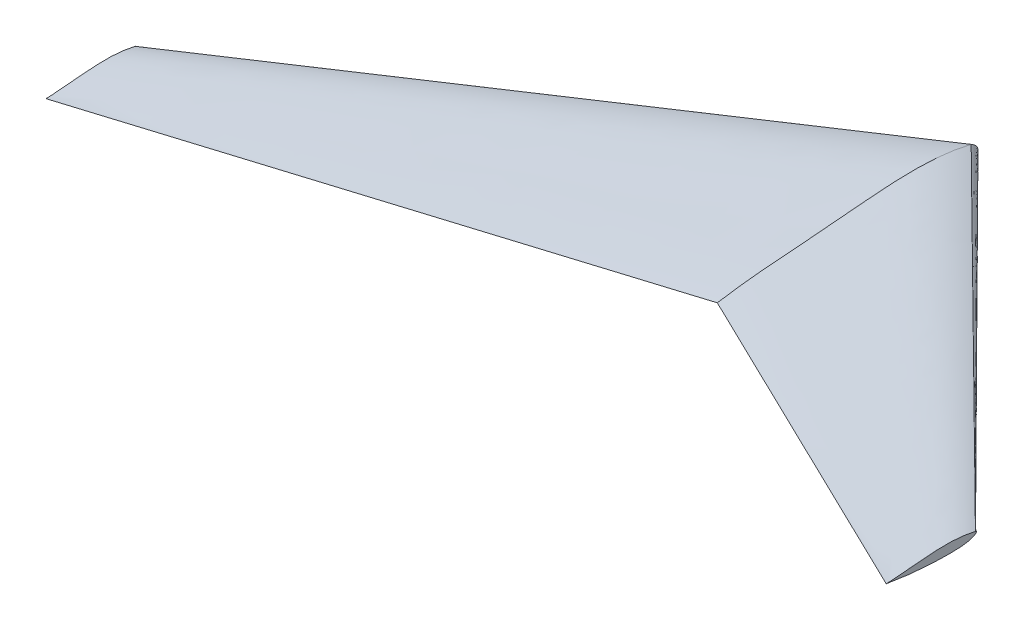
SolidWorks part; units mm, degrees
ref_plane "Front Plane" through (0, 0, 0) normal (0, 0, 1) x (1, 0, 0)
ref_plane "Top Plane" through (0, 0, 0) normal (0, 1, 0) x (1, 0, 0)
ref_plane "Right Plane" through (0, 0, 0) normal (1, 0, 0) x (0, 0, -1)
sketch "Sketch2" plane through (0, 0, 0) normal (0, 1, 0) x (1, 0, 0)
  line L0 (0, -6122.228) -> (0, 2040.7427)
  line L1 (0, 0) -> (-18096.1342, 0) construction
  line L2 (0, 0) -> (-21640.8, -16307.5125) construction
  line L3 (-21640.8, -18450.2946) -> (-21640.8, -15593.2518)
  line L4 (-21640.8, -15593.2518) -> (0, 2040.7427)
  line L5 (-21640.8, -18450.2946) -> (0, -6122.228)
  line L6 (-9083.802, -5361.1886) -> (-9083.802, -6845.1358) construction
  line L7 (-9083.802, -6845.1358) -> (-9083.802, -11296.9774) construction
  line L8 (-9083.802, -6845.1358) -> (0, -6845.1358) construction
  line L9 (0, 408.1485) -> (-18440.4, -13713.752)
  line L10 (0, -35661.6) -> (-7316.724, -42249.6079) construction
  line L11 (0, -35661.6) -> (-8167.6786, -35661.6) construction
  line L12 (0, -34539.0879) -> (0, -39029.1363)
  line L13 (-7316.724, -43428.2455) -> (-7316.724, -41856.7287)
  line L14 (-7316.724, -41856.7287) -> (0, -34539.0879)
  line L15 (0, -39029.1363) -> (-7316.724, -43428.2455)
  line L16 (-2544.3607, -37083.7674) -> (-2544.3607, -37952.5526) construction
  line L17 (-2544.3607, -37952.5526) -> (-2544.3607, -40558.9084) construction
  line L18 (-2544.3607, -37952.5526) -> (0, -37952.5526) construction
  line L19 (-18440.4, -13713.752) -> (-18440.4, -15898.787)
  line L20 (-18440.4, -15898.787) -> (0, -4489.6339)
  line L21 (0, 408.1485) -> (0, -4489.6339) construction
  line L22 (0, -4489.6339) -> (0, 408.1485) construction
  line L23 (0, 408.1485) -> (0, -2040.7427) construction
  line L24 (0, 408.1485) -> (0, -4489.6339) construction
  line L25 (0, -2040.7427) -> (-18440.4, -14806.2695) construction
  line L26 (0, 408.1485) -> (-21640.8, -16164.6603) construction
  line L27 (-6975.7046, -4933.9377) -> (-6975.7046, -6869.7347) construction
  line L28 (-6975.7046, -6869.7347) -> (-6975.7046, -8805.5317) construction
  line L29 (-6975.7046, -6869.7347) -> (0, -6869.7347) construction
  dimension "Wing Sweep" = 37
  dimension "Half Span" = 21640.8
  dimension "Wing Root" = 8162.9707
  dimension "D4" = 2040.7427
  dimension "Wing Tip" = 2857.0428
  dimension "D6" = 714.2607
  dimension "Wing YBar" = 9083.802
  dimension "Tail Sweep" = 42
  dimension "Tail Root" = 4490.0484
  dimension "D10" = 1122.5121
  dimension "Tail Tip" = 1571.5168
  dimension "D12" = 392.8792
  dimension "D13" = 7316.724
  dimension "Tail Ybar" = 2544.3607
  dimension "First Spar" = 1632.5941
  dimension "Second Spar" = 6530.3766
  dimension "Fuel Tip" = 2185.035
  dimension "Tip Spar" = 571.4086
  dimension "Fuel Ybar" = 6975.7046
  dimension "Fuel Tank Length" = 18440.4
  dimension "Tail Arm" = 35661.6
sketch "Sketch4" plane through (0, 0, 0) normal (0, 1, 0) x (1, 0, 0)
  line L0 (0, 17538.8642) -> (0, -40677.9358) construction
  line L1 (-2194.56, 17538.8642) -> (2194.56, 17538.8642) construction
  line L2 (-2194.56, 10955.1842) -> (-2194.56, -31899.6958)
  line L3 (-2194.56, -40677.9358) -> (2194.56, -40677.9358) construction
  line L4 (2194.56, 10955.1842) -> (2194.56, -31899.6958)
  line L5 (0, -6122.228) -> (0, 2040.7427) construction
  line L6 (-9083.802, -6845.1358) -> (0, -6845.1358) construction
  line L7 (-2544.3607, -37952.5526) -> (0, -37952.5526) construction
  line L8 (0, 0) -> (-21640.8, -16307.5125) construction
  line L9 (-21640.8, -15593.2518) -> (0, 2040.7427) construction
  line L10 (-8474.964, 1555.5245) -> (-5807.964, 1555.5245)
  line L11 (-8474.964, 1555.5245) -> (-8474.964, -5453.2245)
  line L12 (-8474.964, -5453.2245) -> (-5807.964, -5453.2245)
  line L13 (-5807.964, 1555.5245) -> (-5807.964, -5453.2245)
  line L14 (2194.56, 10955.1842) -> (-2194.56, 10955.1842)
  arc A0 (-2194.56, -31899.6958) -> (2194.56, -31899.6958) centre (0, -31899.6958) ccw construction
  spline S0 degree 2 poles (-2194.56, 10955.1842) (-2319.3121, 14550.827) (0, 17538.8642) knots 0 0 0 1 1 1 construction
  spline S1 degree 2 poles (2194.56, 10955.1842) (2319.3121, 14550.827) (0, 17538.8642) knots 0 0 0 1 1 1 construction
  spline S2 degree 3 poles (-2194.56, -31899.6958) (-2185.0252, -17343.0176) (-1882.3736, -55849.4008) (-475.0937, -22625.7195) (0, -39029.1363) knots 0 0 0 0 0.566127 1 1 1 1 construction
  spline S3 degree 3 poles (2194.56, -31899.6958) (2185.0252, -17343.0176) (1882.3736, -55849.4008) (475.0937, -22625.7195) (0, -39029.1363) knots 0 0 0 0 0.566127 1 1 1 1 construction
  spline S4 degree 2 poles (-2194.56, -31899.6958) (-4104.2514, -24790.3016) (0, -27753.3552) knots 0 0 0 1 1 1
  spline S5 degree 2 poles (2194.56, -31899.6958) (4104.2514, -24790.3016) (0, -27753.3552) knots 0 0 0 1 1 1
  point P6 (0, 10955.1842)
  point P7 (0, -31899.6958)
  point P8 (0, -6845.1358)
  point P15 (0, -34094.2558)
  point P28 (-7141.464, 1555.5245)
  point P29 (-7141.464, -3778.4755)
  point P35 (-7141.464, -5381.4791)
  point P44 (-7141.464, -1247.9751)
  dimension "Fuse Length" = 58216.8
  dimension "Fuse Dia" = 4389.12
  dimension "D3" = 6583.68
  dimension "D4" = 8778.24
  dimension "D6" = 7141.464
  dimension "Engine Dia" = 2667
  dimension "Engine Length" = 7008.749
  dimension "D9" = 5334
  dimension "D10" = 2803.4996
  dimension "D11" = 5597.1607
  dimension "D2" = 24384
ref_plane "Plane1" through (0, 609.6, 0) normal (0, 1, 0) x (1, 0, 0)
sketch "Sketch10" plane through (0, 0, 0) normal (0, 1, 0) x (1, 0, 0)
  line L0 (-21640.8, -15593.2518) -> (-2194.56, 252.5066)
  line L1 (-2194.56, 10955.1842) -> (-2194.56, -31899.6958) construction
  line L2 (-21640.8, -15593.2518) -> (-21640.8, -18450.2946)
  line L3 (-21640.8, -18450.2946) -> (-7141.464, -10190.49)
  line L4 (-7141.464, -10190.49) -> (-2194.56, -10190.49)
  line L5 (-21640.8, -18450.2946) -> (0, -6122.228) construction
  line L6 (-21640.8, -15593.2518) -> (0, 2040.7427) construction
  line L7 (-2194.56, -10190.49) -> (-2194.56, 252.5066) construction
  line L9 (0, 271.2873) -> (0, -10190.49)
  line L10 (0, -10190.49) -> (-2194.56, -10190.49)
  line L11 (0, -6122.228) -> (0, 2040.7427) construction
  line L12 (-2194.56, 252.5066) -> (0, 2040.7427)
  line L13 (0, 2040.7427) -> (0, 271.2873)
ref_plane "Plane4" through (17269.5438, 0, 17267.3802) normal (0.7072, 0, 0.7071) x (0.7071, 0, -0.7072)
ref_plane "Plane2" through (-7316.724, 0, 0) normal (1, 0, 0) x (0, 0, -1)
sketch "Sketch11" plane through (0, 0, 0) normal (1, 0, 0) x (0, 0, -1)
  line L0 (-31394.1382, -352.4096) -> (-30857.4716, -352.4096) construction
  line L1 (-34539.0879, 0) -> (-39029.1363, 0) construction
  spline S0 degree 3 poles (-39051.8309, 0) (-38403.1581, 109.7274) (-36924.0487, 165.2873) (-35448.5779, 379.0643) (-34630.3278, 179.2815) knots 0 0 0 0 0.443797 1 1 1 1
  spline S1 degree 3 poles (-39051.8309, 0) (-38190.4109, -219.3036) (-37292.2896, -199.7787) (-36415.6545, -314.689) knots 0 0 0 0 1 1 1 1
  spline S2 degree 3 poles (-36415.6545, -314.689) (-35966.3296, -355.4965) (-35302.3779, -490.2862) (-34639.9796, -191.5367) (-34412.4231, 59.404) (-34630.3278, 179.2815) knots 0 0 0 0 0.638862 0.803347 1 1 1 1
  point P10 (-34515.8257, 0)
  point P15 (-34663.7072, -171.4719)
  point P17 (-34808.7963, -419.3177)
  point P19 (-34630.3278, 179.2815)
  point P20 (-35740.7984, 288.8166)
  point P21 (-34993.6769, -332.8541)
  point P22 (-35620.3503, -338.1589)
  point P23 (-36036.1804, -262.9766)
  point P24 (-38520.4042, -107.5889)
  point P25 (-36231.1744, -238.4822)
  point P26 (-35820.287, -378.7212)
  point P27 (-36415.6545, -314.689)
sketch "Sketch12" plane through (17269.5438, 0, 17267.3802) normal (0.7072, 0, 0.7071) x (0.7071, 0, -0.7072)
  line L0 (-24430.9437, -230.124) -> (-34772.4118, 1522.4358)
  line L1 (-24430.9437, 230.124) -> (-34772.4118, 1683.5226)
  line L2 (-24430.9437, 230.124) -> (-24430.9437, -230.124) construction
  line L3 (-34772.4118, 1683.5226) -> (-34772.4118, 1522.4358) construction
  line L4 (-24424.3532, 0) -> (-27599.4958, 0) construction
  line L5 (-34772.4118, 1683.5226) -> (-29601.6778, 1683.5226) construction
  point P1 (-24430.9437, 0)
  dimension "D2" = 460.248
  dimension "D1" = 161.0868
  dimension "D3" = 8
sketch "Sketch13" plane through (-7316.724, 0, 0) normal (1, 0, 0) x (0, 0, -1)
  line L0 (-34331.3091, -72.3608) -> (-33794.6424, -72.3608) construction
  spline S0 degree 2 poles (-41855.2375, 1608.2545) (-41861.219, 1619.2984) (-41873.5941, 1621.3118) knots 0 0 0 1 1 1
  spline S1 degree 3 poles (-41855.2375, 1608.2545) (-41858.8786, 1595.1115) (-41880.4209, 1575.3781) (-41934.0507, 1548.2168) (-42017.7704, 1527.6333) (-42150.8328, 1512.0914) (-42318.4831, 1508.4982) (-42753.5374, 1514.7801) (-43124.4968, 1555.3993) (-43425.9997, 1607.871) knots 0 0 0 0 0.024793 0.052363 0.112618 0.184636 0.303441 0.426297 1 1 1 1
  spline S2 degree 3 poles (-43425.9997, 1607.871) (-43371.1182, 1606.7565) (-43276.8689, 1616.0887) (-43112.0017, 1630.104) (-42910.3773, 1646.0561) (-42487.6371, 1686.2082) (-42131.8895, 1685.4323) (-41873.5941, 1621.3118) knots 0 0 0 0 0.105305 0.182318 0.318577 0.494689 1 1 1 1
  point P8 (-43428.2455, 0)
loft "Loft1" add profiles "Sketch13", "Sketch11" connector at (-7316.724, 1607.871, 43425.9997) connector at (0, 0, 39051.8309)
mirror "Mirror1" about plane through (0, 0, 0) normal (1, 0, 0) of bodies 130
equation "\"D6@Sketch2\" = \"Wing Tip@Sketch2\" / 4"
equation "\"D4@Sketch2\" = \"Wing Root@Sketch2\" / 4"
equation "\"D10@Sketch2\" = \"Tail Root@Sketch2\" / 4"
equation "\"D12@Sketch2\" = \"Tail Tip@Sketch2\" / 4"
equation "\"D13@Sketch2\"=48.01/2"
equation "\"First Spar@Sketch2\"=0.2 * \"Wing Root@Sketch2\""
equation "\"Second Spar@Sketch2\" = 0.8 * \"Wing Root@Sketch2\""
equation "\"Tip Spar@Sketch2\"=0.2 * \"Wing Tip@Sketch2\""
equation "\"D3@Sketch4\" = 1.5 * \"Fuse Dia@Sketch4\""
equation "\"D4@Sketch4\" = 2 * \"Fuse Dia@Sketch4\""
equation "\"D6@Sketch4\" = 0.33 * \"Half Span@Sketch2\""
equation "\"D9@Sketch4\" = 2 * \"Engine Dia@Sketch4\""
equation "\"D10@Sketch4\" = 0.40 * \"Engine Length@Sketch4\""
equation "\"D1@Sketch12\"=0.35*\"D2@Sketch12\""
